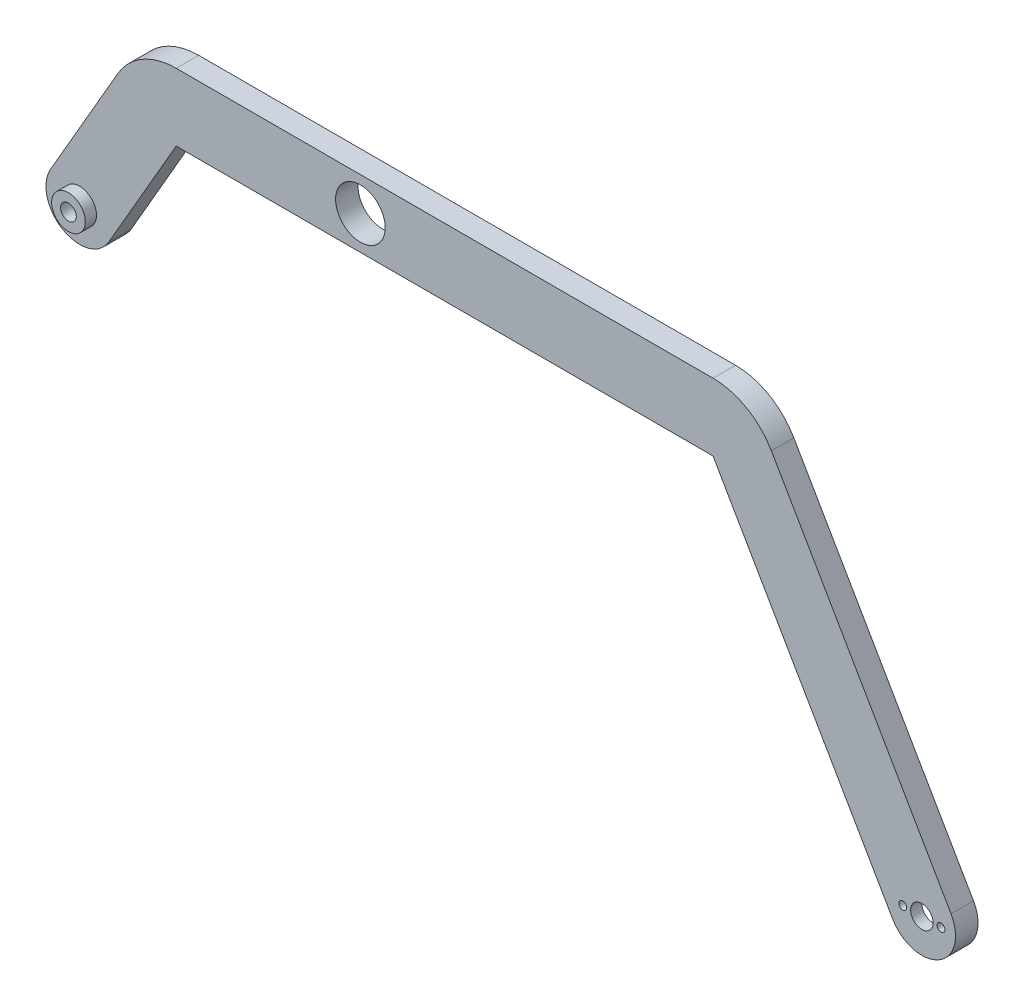
SolidWorks part; units mm, degrees
ref_plane "Front Plane" through (0, 0, 0) normal (0, 0, 1) x (1, 0, 0)
ref_plane "Top Plane" through (0, 0, 0) normal (0, 1, 0) x (1, 0, 0)
ref_plane "Right Plane" through (0, 0, 0) normal (1, 0, 0) x (0, 0, -1)
sketch "Sketch1" plane through (0, 0, 0) normal (0, 0, 1) x (1, 0, 0)
  line L0 (0, -15) -> (0, 15) construction
  line L4 (-82.0096, -15) -> (-112.0096, -66.9615)
  line L6 (-137.9904, -51.9615) -> (-107.9904, 0)
  line L7 (262.9904, -138.5641) -> (182.9904, 0)
  line L9 (157.0096, -15) -> (237.0096, -153.5641)
  line L10 (0, 15) -> (157.0096, 15)
  line L11 (0, -15) -> (157.0096, -15)
  line L12 (0, 15) -> (-82.0096, 15)
  line L13 (0, -15) -> (-82.0096, -15)
  line L14 (237.0096, -153.5641) -> (262.9904, -138.5641) construction
  line L15 (-137.9904, -51.9615) -> (-112.0096, -66.9615) construction
  arc A1 (-107.9904, 0) -> (-82.0096, 15) centre (-82.0096, -15) cw
  arc A2 (182.9904, 0) -> (157.0096, 15) centre (157.0096, -15) ccw
  arc A6 (237.0096, -153.5641) -> (262.9904, -138.5641) centre (250, -146.0641) ccw
  arc A7 (-137.9904, -51.9615) -> (-112.0096, -66.9615) centre (-125, -59.4615) ccw
  circle A8 centre (258.5, -146.0433) radius 1.75
  circle A9 centre (241.5, -146.0848) radius 1.75
  point P4 (0, 0)
  point P7 (0, -15)
  point P20 (0, 15)
  dimension "D2" = 60
  dimension "D6" = 3.5
  dimension "D7" = 3.5
  dimension "D1" = 30
  dimension "D3" = 250
  dimension "D4" = 160
  dimension "D5" = 125
extrude "Boss-Extrude1" add sketch "Sketch1" along normal blind 10
sketch "Sketch2" plane through (0, 0, 10) normal (0, 0, 1) x (1, 0, 0)
  circle A1 centre (250, -146.0641) radius 5
  circle A2 centre (0, 0) radius 11.0625
  dimension "D1" = 22.125
extrude "Cut-Extrude1" cut sketch "Sketch2" against normal up to surface (10 mm away) up to face at (260.25, -146.0433, 0)
sketch "Sketch3" plane through (0, 0, 0) normal (0, 0, -1) x (-1, 0, 0)
  circle A0 centre (0, 0) radius 12
sketch "Sketch4" plane through (0, 0, 0) normal (0, 0, -1) x (-1, 0, 0)
  circle A0 centre (-250, -146.0641) radius 13
  dimension "D1" = 26
extrude "Cut-Extrude2" cut sketch "Sketch4" against normal offset from surface (5 mm away) 5 up to face at (255, -146.0641, 10)
sketch "Sketch8" plane through (0, 0, 10) normal (0, 0, 1) x (1, 0, 0)
  circle A0 centre (-125, -59.4615) radius 7.5
  dimension "D1" = 15
extrude "Boss-Extrude2" add sketch "Sketch8" along normal blind 5
sketch "Sketch9" plane through (0, 0, 15) normal (0, 0, 1) x (1, 0, 0)
  circle A0 centre (-125, -59.4615) radius 3.5
  dimension "D1" = 7
extrude "Cut-Extrude3" cut sketch "Sketch9" against normal through all
